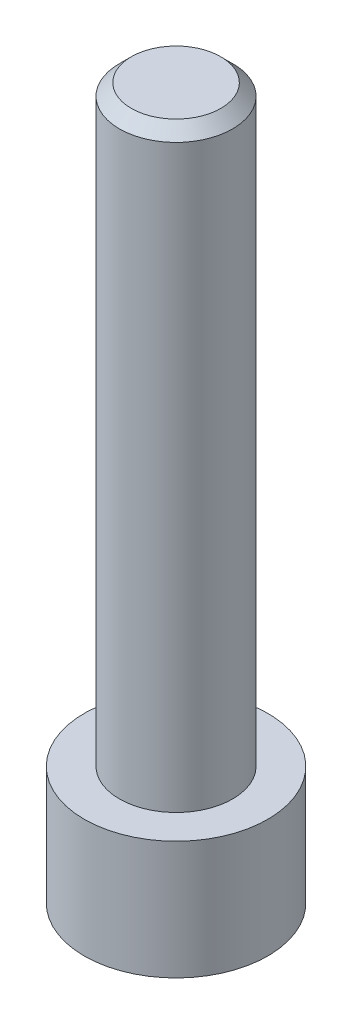
SolidWorks part; units mm, degrees
ref_plane "Front Plane" through (0, 0, 0) normal (0, 0, 1) x (1, 0, 0)
ref_plane "Top Plane" through (0, 0, 0) normal (0, 1, 0) x (1, 0, 0)
ref_plane "Right Plane" through (0, 0, 0) normal (1, 0, 0) x (0, 0, -1)
sketch "Sketch1" plane through (0, 0, 0) normal (0, 1, 0) x (1, 0, 0)
  line L1 (4.4745, 0) -> (2.2372, 3.875) construction
  line L2 (2.2372, 3.875) -> (-2.2372, 3.875) construction
  line L3 (-2.2372, 3.875) -> (-4.4745, 0) construction
  line L4 (-4.4745, 0) -> (-2.2372, -3.875) construction
  line L5 (-2.2372, -3.875) -> (2.2372, -3.875) construction
  line L6 (2.2372, -3.875) -> (4.4745, 0) construction
  circle A0 centre (0, 0) radius 3.875
  dimension "D1" = 7.75
extrude "Boss-Extrude1" add sketch "Sketch1" along normal blind 30
sketch "Sketch2" plane through (0, 30, 0) normal (0, 1, 0) x (1, 0, 0)
  circle A0 centre (0, 0) radius 2.39
  dimension "D1" = 4.78
extrude "Cut-Extrude1" cut sketch "Sketch2" against normal blind 25 flip side to cut
ref_axis "Axis1" through (0, 5, 0) along (0, 1, 0)
chamfer "Chamfer1" distance 0.5 angle 45 1 edges at (0, 30, 2.39)
sketch "Sketch5" plane through (0, 30, 0) normal (0, 1, 0) x (1, 0, 0)
  circle A0 centre (0, 0) radius 2.39
  dimension "D1" = 4.78
curve "Helix/Spiral1" pitch 0.7 height 25 turns 35.7143
ref_plane "Plane1" through (0, 30, 2.39) normal (-0.9989, -0.0466, 0) x (0, 0, 1)
sketch "Sketch8" plane through (0, 0, 0) normal (0, -1, 0) x (1, 0, 0)
  line L1 (2.6443, 0) -> (1.3221, 2.29)
  line L2 (1.3221, 2.29) -> (-1.3221, 2.29)
  line L3 (-1.3221, 2.29) -> (-2.6443, 0)
  line L4 (-2.6443, 0) -> (-1.3221, -2.29)
  line L5 (-1.3221, -2.29) -> (1.3221, -2.29)
  line L6 (1.3221, -2.29) -> (2.6443, 0)
  circle A0 centre (0, 0) radius 2.29 construction
  dimension "D1" = 4.58
extrude "Cut-Extrude2" cut sketch "Sketch8" against normal blind 3.36
